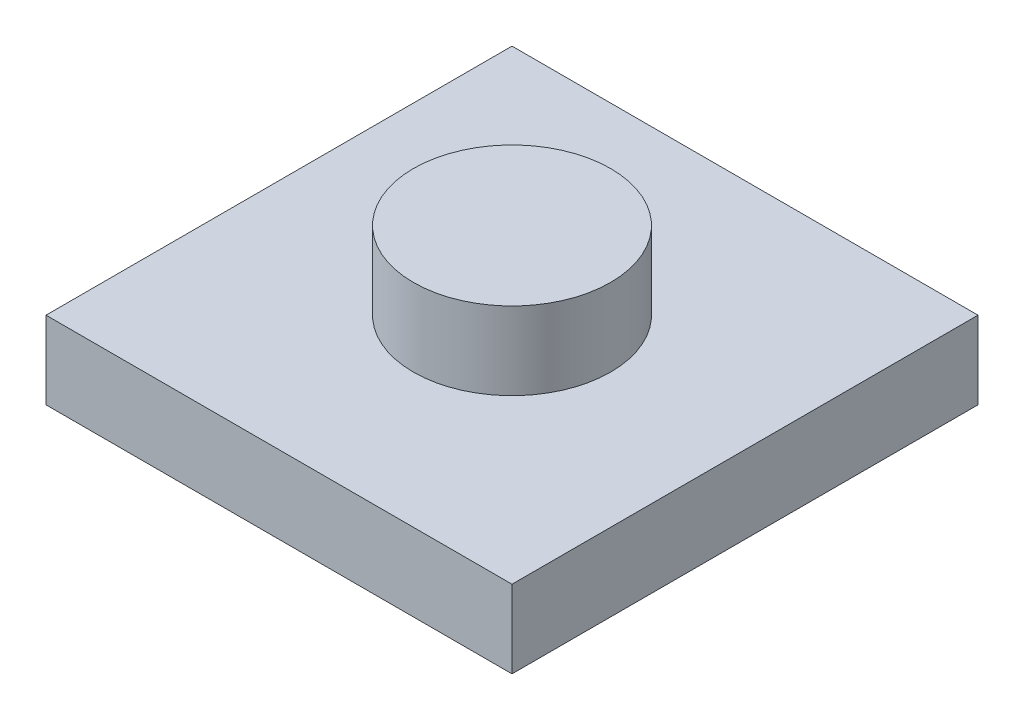
SolidWorks part; units mm, degrees
ref_plane "Front Plane" through (0, 0, 0) normal (0, 0, 1) x (1, 0, 0)
ref_plane "Top Plane" through (0, 0, 0) normal (0, 1, 0) x (1, 0, 0)
ref_plane "Right Plane" through (0, 0, 0) normal (1, 0, 0) x (0, 0, -1)
sketch "Sketch1" plane through (0, 0, 0) normal (0, 1, 0) x (1, 0, 0)
  line L1 (45, -45) -> (-45, -45)
  line L2 (45, -45) -> (45, 45)
  line L3 (45, 45) -> (-45, 45)
  line L4 (-45, -45) -> (-45, 45)
  line L5 (45, -45) -> (-45, 45) construction
  line L6 (45, 45) -> (-45, -45) construction
  circle A0 centre (0, 0) radius 19.05
  point P0 (0, 0)
  dimension "D1" = 90
extrude "Boss-Extrude1" add sketch "Sketch1" along normal blind 15
extrude "Boss-Extrude2" add sketch "Sketch1<2>" along normal blind 30 contours A0 region at (0, 0, 0)
sketch "Sketch1<2>" plane through (0, 0, 0) normal (0, 1, 0) x (1, 0, 0) same geometry as "Sketch1"
cosmetic thread "Cosmetic Thread1" parameters "D1"=15, "D2"=33.797
